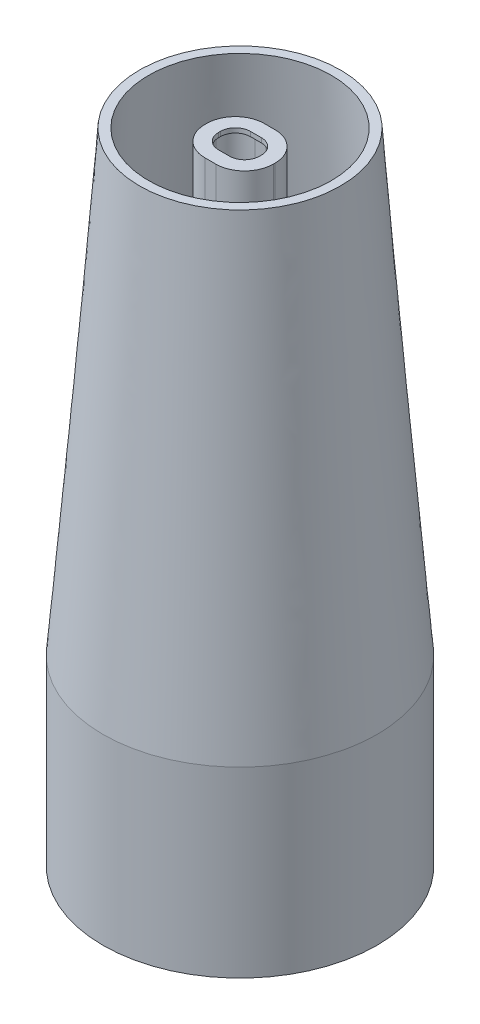
SolidWorks part; units mm, degrees
ref_plane "Front Plane" through (0, 0, 0) normal (0, 0, 1) x (1, 0, 0)
ref_plane "Top Plane" through (0, 0, 0) normal (0, 1, 0) x (1, 0, 0)
ref_plane "Right Plane" through (0, 0, 0) normal (1, 0, 0) x (0, 0, -1)
sketch "Esboço1" plane through (0, 0, 0) normal (0, 1, 0) x (1, 0, 0)
  circle A0 centre (0, 0) radius 15
  dimension "D1" = 30
extrude "Ressalto-extrusão1" add sketch "Esboço1" along normal blind 20
sketch "Esboço2" plane through (0, 20, 0) normal (0, 1, 0) x (1, 0, 0)
  circle A0 centre (0, 0) radius 14
  circle A1 centre (0, 0) radius 15 construction
  dimension "D1" = 1
extrude "Corte-extrusão1" cut sketch "Esboço2" against normal blind 17
ref_plane "Plano2" through (0, 20, 0) normal (0, 1, 0) x (1, 0, 0)
sketch "Esboço11" plane through (0, 20, 0) normal (0, 1, 0) x (1, 0, 0)
  circle A0 centre (0, 0) radius 14 construction
  circle A1 centre (0, 0) radius 15 construction
  circle A2 centre (0, 0) radius 14
  circle A3 centre (0, 0) radius 15
ref_plane "Plano3" through (0, 70, 0) normal (0, 1, 0) x (1, 0, 0)
sketch "Esboço12" plane through (0, 70, 0) normal (0, 1, 0) x (1, 0, 0)
  circle A0 centre (0, 0) radius 10
  circle A1 centre (0, 0) radius 11
  dimension "D1" = 20
  dimension "D2" = 1
loft "Loft2" add section "Esboço12" section "Esboço11" connector at (-10.9986, 70, -0.1781) connector at (-14.6845, 20, 3.0603)
loft "Loft de corte1" cut section "Esboço12<3>" section "Esboço11<3>" connector at (-9.9721, 70, -0.747) connector at (-13.7284, 20, 2.7442)
sketch "Esboço12<3>" plane through (0, 70, 0) normal (0, 1, 0) x (1, 0, 0) same geometry as "Esboço12"
sketch "Esboço11<3>" plane through (0, 20, 0) normal (0, 1, 0) x (1, 0, 0) same geometry as "Esboço11"
sketch "Esboço3" plane through (0, 3, 0) normal (0, 1, 0) x (1, 0, 0)
  line L0 (-3.75, -0.1) -> (-3.75, 0.1)
  line L1 (-0.6, -2.25) -> (0.6, -2.25)
  line L2 (-2.75, -0.1) -> (-2.75, 0.1)
  line L3 (-0.6, 2.25) -> (0.6, 2.25)
  line L4 (2.75, -0.1) -> (2.75, 0.1)
  line L5 (-0.6, -3.25) -> (0.6, -3.25)
  line L6 (3.75, -0.1) -> (3.75, 0.1)
  line L7 (-0.6, 3.25) -> (0.6, 3.25)
  arc A4 (2.75, 0.1) -> (0.6, 2.25) centre (0.6, 0.1) ccw
  arc A5 (2.75, -0.1) -> (0.6, -2.25) centre (0.6, -0.1) cw
  arc A6 (-0.6, -2.25) -> (-2.75, -0.1) centre (-0.6, -0.1) cw
  arc A7 (-0.6, 2.25) -> (-2.75, 0.1) centre (-0.6, 0.1) ccw
  arc A8 (-0.6, 3.25) -> (-3.75, 0.1) centre (-0.6, 0.1) ccw
  arc A9 (-0.6, -3.25) -> (-3.75, -0.1) centre (-0.6, -0.1) cw
  arc A10 (3.75, -0.1) -> (0.6, -3.25) centre (0.6, -0.1) cw
  arc A11 (3.75, 0.1) -> (0.6, 3.25) centre (0.6, 0.1) ccw
  point P0 (0, 0)
  point P12 (0, 2.25)
  point P15 (2.75, 0)
  dimension "D3" = 2.15
  dimension "D4" = 1
  dimension "D1" = 4.5
  dimension "D2" = 5.5
extrude "Ressalto-extrusão2" add sketch "Esboço3" along normal blind 65
sketch "Esboço5" plane through (0, 0, 0) normal (0, 1, 0) x (1, 0, 0)
  line L8 (0.6, 2.25) -> (-0.6, 2.25)
  line L9 (0.6, 2.25) -> (-0.6, 2.25)
  line L10 (-2.75, 0.1) -> (-2.75, -0.1)
  line L11 (-2.75, 0.1) -> (-2.75, -0.1)
  line L16 (-0.6, -2.25) -> (0.6, -2.25)
  line L17 (-0.6, -2.25) -> (0.6, -2.25)
  line L18 (2.75, -0.1) -> (2.75, 0.1)
  line L19 (2.75, -0.1) -> (2.75, 0.1)
  arc A3 (2.75, 0.1) -> (0.6, 2.25) centre (0.6, 0.1) ccw
  arc A8 (2.75, 0.1) -> (0.6, 2.25) centre (0.6, 0.1) ccw
  arc A9 (-0.6, 2.25) -> (-2.75, 0.1) centre (-0.6, 0.1) ccw
  arc A14 (-0.6, 2.25) -> (-2.75, 0.1) centre (-0.6, 0.1) ccw
  arc A15 (-2.75, -0.1) -> (-0.6, -2.25) centre (-0.6, -0.1) ccw
  arc A16 (-2.75, -0.1) -> (-0.6, -2.25) centre (-0.6, -0.1) ccw
  arc A17 (0.6, -2.25) -> (2.75, -0.1) centre (0.6, -0.1) ccw
  arc A18 (0.6, -2.25) -> (2.75, -0.1) centre (0.6, -0.1) ccw
  dimension "D1" = 0
extrude "Corte-extrusão4" cut sketch "Esboço5" against normal through all both and the other way through all
sketch "Esboço6" plane through (0, 3, 0) normal (0, 1, 0) x (1, 0, 0)
  line L0 (-14, 0) -> (-3.75, 0) construction
  line L1 (-3.75, 0.1) -> (-3.75, -0.1) construction
  circle A0 centre (0, 0) radius 8.875 construction
  circle A2 centre (0, 0) radius 14 construction
  circle A4 centre (0, 8.875) radius 3
  circle A5 centre (0, 8.875) radius 4
  circle A6 centre (0, 0) radius 8.875 construction
  circle A7 centre (7.686, -4.4375) radius 3
  circle A8 centre (7.686, -4.4375) radius 4
  circle A9 centre (0, 0) radius 8.875 construction
  circle A10 centre (-7.686, -4.4375) radius 3
  circle A11 centre (-7.686, -4.4375) radius 4
  point P12 (-8.875, 0)
  point P29 (0, 0)
  dimension "D1" = 6
  dimension "D2" = 1
  dimension "D3" = 3
extrude "Ressalto-extrusão3" add sketch "Esboço6" along normal blind 5
sketch "Esboço9" plane through (0, 0, 0) normal (0, 1, 0) x (1, 0, 0)
  circle A0 centre (0, 0) radius 8.875 construction
  circle A3 centre (0, 8.875) radius 3
  circle A4 centre (0, 8.875) radius 3
  circle A6 centre (7.686, -4.4375) radius 3
  circle A7 centre (-7.686, -4.4375) radius 3
  point P9 (0, 0)
  point P17 (0, 0)
  dimension "D1" = 0
  dimension "D2" = 3
extrude "Corte-extrusão5" cut sketch "Esboço9" along normal blind 5
fillet "Filete4" radius 1 12 edges at (-2.8274, 3, 2.3274) (0, 3, 3.25) (2.8274, 3, 2.3274) (3.75, 3, 0) (2.8274, 3, -2.3274) (0, 3, -3.25) (-2.8274, 3, -2.3274) (-3.75, 3, 0) (0, 3, 14) (-7.686, 3, 8.4375) (7.686, 3, 8.4375) (0, 3, -4.875)
sketch "Esboço13" plane through (0, 8, 0) normal (0, 1, 0) x (1, 0, 0)
  circle A0 centre (0, 8.875) radius 2.75
  circle A1 centre (0, 8.875) radius 4 construction
  circle A2 centre (0, 8.875) radius 4
  circle A3 centre (7.686, -4.4375) radius 4
  circle A4 centre (7.686, -4.4375) radius 2.75
  circle A5 centre (-7.686, -4.4375) radius 4
  circle A6 centre (-7.686, -4.4375) radius 2.75
  dimension "D1" = 5.5
  dimension "D2" = 3
extrude "Ressalto-extrusão4" add sketch "Esboço13" along normal blind 0.5
sketch "Esboço14" plane through (0, 68, 0) normal (0, 1, 0) x (1, 0, 0)
  line L0 (-3.75, 0.1) -> (-3.75, -0.1) construction
  line L1 (-0.6, -3.25) -> (0.6, -3.25) construction
  line L2 (3.75, -0.1) -> (3.75, 0.1) construction
  line L3 (0.6, 3.25) -> (-0.6, 3.25) construction
  line L4 (-3.75, 0.1) -> (-3.75, -0.1)
  line L5 (-0.6, -3.25) -> (0.6, -3.25)
  line L6 (3.75, -0.1) -> (3.75, 0.1)
  line L7 (0.6, 3.25) -> (-0.6, 3.25)
  line L8 (0.6, 1.75) -> (-0.6, 1.75)
  line L9 (-2.25, 0.1) -> (-2.25, -0.1)
  line L10 (-0.6, -1.75) -> (0.6, -1.75)
  line L11 (2.25, -0.1) -> (2.25, 0.1)
  arc A0 (-3.75, -0.1) -> (-0.6, -3.25) centre (-0.6, -0.1) ccw construction
  arc A1 (0.6, -3.25) -> (3.75, -0.1) centre (0.6, -0.1) ccw construction
  arc A2 (3.75, 0.1) -> (0.6, 3.25) centre (0.6, 0.1) ccw construction
  arc A3 (-0.6, 3.25) -> (-3.75, 0.1) centre (-0.6, 0.1) ccw construction
  arc A4 (-3.75, -0.1) -> (-0.6, -3.25) centre (-0.6, -0.1) ccw
  arc A5 (0.6, -3.25) -> (3.75, -0.1) centre (0.6, -0.1) ccw
  arc A6 (3.75, 0.1) -> (0.6, 3.25) centre (0.6, 0.1) ccw
  arc A7 (-0.6, 3.25) -> (-3.75, 0.1) centre (-0.6, 0.1) ccw
  arc A8 (2.25, 0.1) -> (0.6, 1.75) centre (0.6, 0.1) ccw
  arc A9 (-0.6, 1.75) -> (-2.25, 0.1) centre (-0.6, 0.1) ccw
  arc A10 (-2.25, -0.1) -> (-0.6, -1.75) centre (-0.6, -0.1) ccw
  arc A11 (0.6, -1.75) -> (2.25, -0.1) centre (0.6, -0.1) ccw
  dimension "D1" = 1.5
extrude "Ressalto-extrusão5" add sketch "Esboço14" along normal blind 0.5
